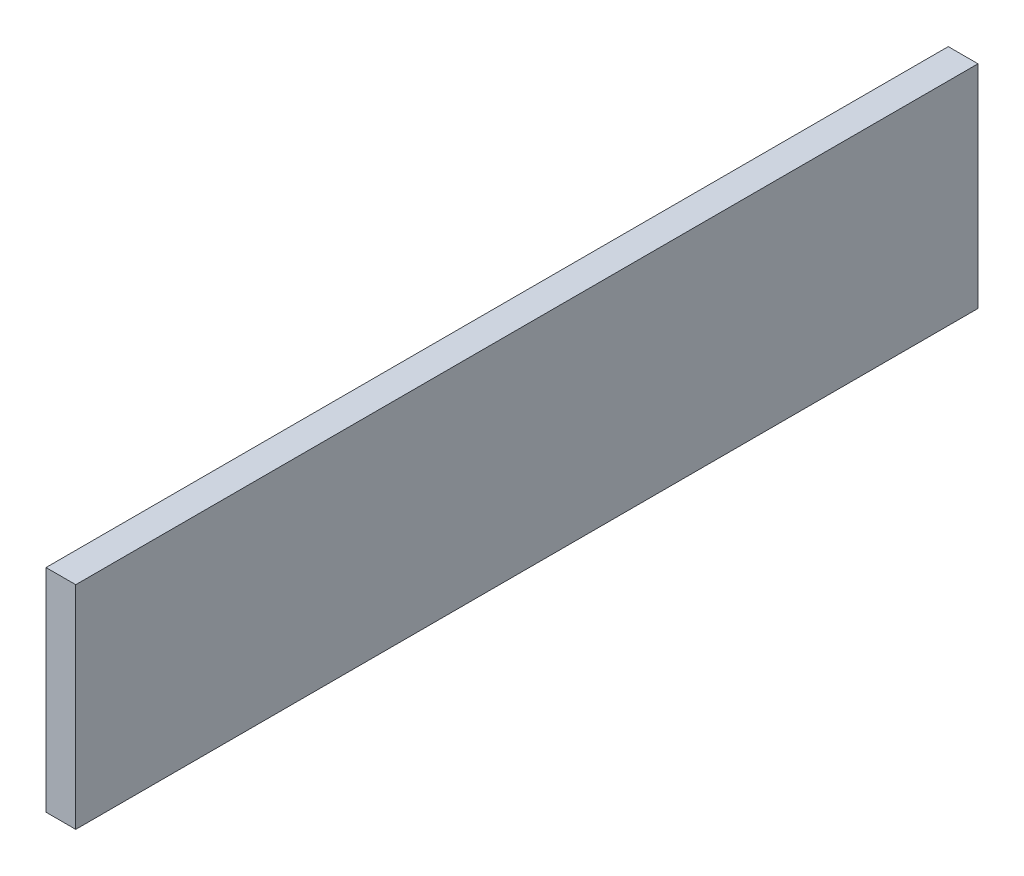
SolidWorks part; units mm, degrees
ref_plane "Front" through (0, 0, 0) normal (0, 0, 1) x (1, 0, 0)
ref_plane "Top" through (0, 0, 0) normal (0, 1, 0) x (1, 0, 0)
ref_plane "Right" through (0, 0, 0) normal (1, 0, 0) x (0, 0, -1)
sketch "Sketch1" plane through (0, 0, 0) normal (0, 1, 0) x (1, 0, 0)
  line L1 (0, 0) -> (76.2, 0)
  line L2 (0, 0) -> (0, 2311.4)
  line L3 (0, 2311.4) -> (76.2, 2311.4)
  line L4 (76.2, 0) -> (76.2, 2311.4)
  dimension "D1" = 2311.4
  dimension "D2" = 76.2
extrude "Boss-Extrude1" add sketch "Sketch1" along normal blind 542.925
